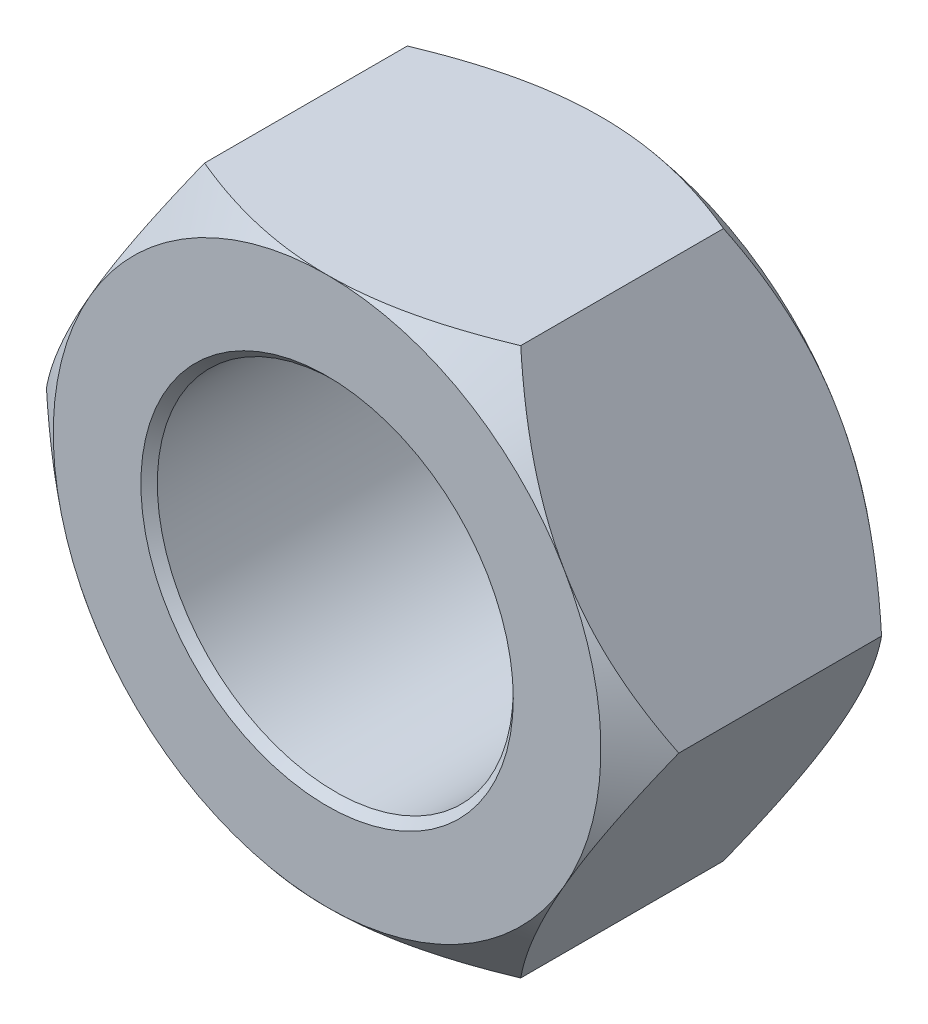
SolidWorks part; units mm, degrees
ref_plane "Front Plane" through (0, 0, 0) normal (0, 0, 1) x (1, 0, 0)
ref_plane "Top Plane" through (0, 0, 0) normal (0, 1, 0) x (1, 0, 0)
ref_plane "Right Plane" through (0, 0, 0) normal (1, 0, 0) x (0, 0, -1)
sketch "Sketch1" plane through (0, 0, 0) normal (0, 0, 1) x (1, 0, 0)
  line L1 (-11.547, 0) -> (-5.7735, -10)
  line L2 (-5.7735, -10) -> (5.7735, -10)
  line L3 (5.7735, -10) -> (11.547, 0)
  line L4 (11.547, 0) -> (5.7735, 10)
  line L5 (5.7735, 10) -> (-5.7735, 10)
  line L6 (-5.7735, 10) -> (-11.547, 0)
  circle A0 centre (0, 0) radius 10 construction
  circle A1 centre (0, 0) radius 6.5
  dimension "D1" = 13
  dimension "D2" = 20
extrude "Boss-Extrude1" add sketch "Sketch1" along normal blind 10
sketch "Sketch2" plane through (0, 0, 10) normal (0, 0, 1) x (1, 0, 0)
  line L0 (-5.7735, 10) -> (-11.547, 0) construction
  circle A0 centre (0, 0) radius 10
extrude "Cut-Extrude1" cut sketch "Sketch2" against normal blind 3 draft 50 flip side to cut
ref_plane "Plane1" through (0, 0, 5) normal (0, 0, -1) x (-1, 0, 0)
mirror "Mirror1" about plane through (0, 0, 5) normal (0, 0, -1) of "Cut-Extrude1"
ref_axis "Axis1" through (0, 0, 10) along (0, 0, -1)
chamfer "Chamfer1" distance 0.3 angle 45 2 edges at (6.5, 0, 0) (6.5, 0, 10)
